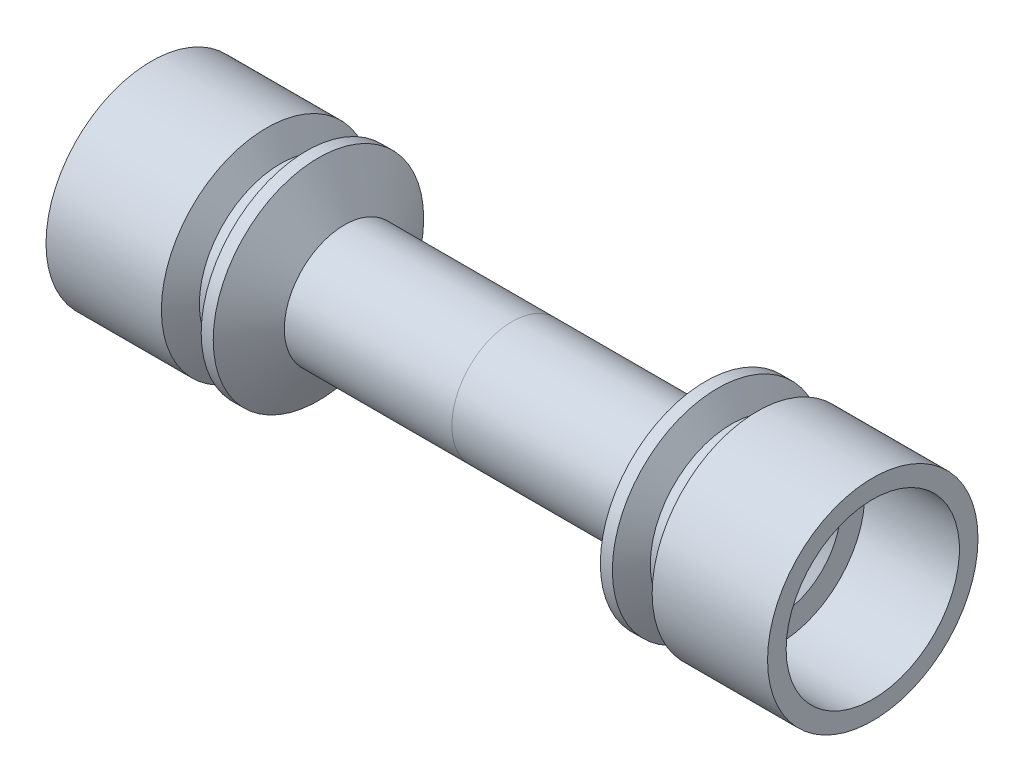
SolidWorks part; units mm, degrees
ref_plane "Front Plane" through (0, 0, 0) normal (0, 0, 1) x (1, 0, 0)
ref_plane "Top Plane" through (0, 0, 0) normal (0, 1, 0) x (1, 0, 0)
ref_plane "Right Plane" through (0, 0, 0) normal (1, 0, 0) x (0, 0, -1)
sketch "Sketch2" plane through (0, 0, 0) normal (0, 0, 1) x (1, 0, 0)
  line L0 (0, 0) -> (0, 28.4375) construction
  line L1 (-19.05, 4.575) -> (-14.05, 4.575) construction
  line L2 (-19.05, 4.575) -> (-19.05, -4.575) construction
  line L3 (-19.05, -4.575) -> (-14.05, -4.575) construction
  line L4 (-14.05, 4.575) -> (-14.05, -4.575) construction
  line L5 (-19.05, 4.575) -> (-14.05, -4.575) construction
  line L6 (-19.05, -4.575) -> (-14.05, 4.575) construction
  line L7 (14.05, 4.5) -> (49.5332, 4.5) construction
  line L8 (14.05, 4.5) -> (14.05, -4.5) construction
  line L9 (14.05, -4.5) -> (49.5332, -4.5) construction
  line L10 (49.5332, 4.5) -> (49.5332, -4.5) construction
  line L11 (14.05, 4.5) -> (49.5332, -4.5) construction
  line L12 (14.05, -4.5) -> (49.5332, 4.5) construction
  line L13 (-19.05, 0) -> (49.5332, 0) construction
  line L14 (-19.05, 5.5562) -> (-12.957, 5.5562)
  line L21 (-8.8457, 3.175) -> (0, 3.175)
  line L22 (-19.05, 5.5562) -> (-19.05, 4.575)
  line L23 (-19.05, 4.575) -> (-14.05, 4.575)
  line L24 (-14.05, 4.575) -> (-14.05, 0)
  line L25 (-14.05, 0) -> (0, 0)
  line L26 (0, 0) -> (0, 3.175)
  line L27 (-33.5594, -5.5562) -> (-33.5594, 5.5562) construction
  line L28 (-12.957, 5.5562) -> (-12.2238, 4.2863)
  line L29 (-12.2238, 4.2863) -> (-11.5887, 4.2863)
  line L30 (-19.05, 5.5562) -> (19.05, 5.5562) construction
  line L31 (0, 1.6) -> (-12.5, 1.6)
  line L32 (-12.5, 1.6) -> (-14.1, 0)
  line L33 (-12.5, 1.6) -> (-12.5, -1.6) construction
  line L34 (-12.5, 1.6) -> (12.5, 1.6) construction
  line L35 (-14.05, 1.7145) -> (-9.225, 1.7145)
  line L36 (-9.225, 1.7145) -> (-9.225, 0)
  line L37 (-14.05, 3.305) -> (-13.542, 2.797)
  line L38 (-9.225, 1.7145) -> (-22.225, 1.7145) construction
  line L39 (-9.225, 1.7145) -> (-9.225, -1.7145) construction
  line L40 (-9.225, -1.7145) -> (-22.225, -1.7145) construction
  line L41 (-22.225, 1.7145) -> (-22.225, -1.7145) construction
  line L42 (-13.542, 2.797) -> (-13.542, 0)
  line L46 (-11.5887, 4.2863) -> (-10.8555, 5.5563)
  line L47 (-10.8555, 5.5563) -> (-10.2205, 5.5563)
  line L48 (-10.2205, 5.5563) -> (-8.8457, 3.175)
  line L49 (-11.9062, 4.2863) -> (-11.9062, 6.3987) construction
  line L50 (-11.9062, 6.3987) -> (11.9062, 6.3987) construction
  point P0 (-16.55, 0)
  point P5 (31.7916, 0)
  point P27 (-33.5594, 0)
  point P28 (-18.8314, 6.3987)
  point P29 (-12.5, 0)
  point P33 (0, 6.3987)
  point P35 (-18.6093, 5.5562)
  point P36 (0, 1.6)
  point P48 (-9.225, 0)
  point P51 (0, 5.5562)
  point P52 (-20.4916, 6.5757)
  dimension "D3" = 3.175
  dimension "D4" = 11.1125
  dimension "D5" = 9.15
  dimension "D6" = 60
  dimension "D7" = 0.635
  dimension "D8" = 60
  dimension "D9" = 23.8125
  dimension "D10" = 1.27
  dimension "D11" = 38.1
  dimension "D12" = 0.635
  dimension "D13" = 45
  dimension "D14" = 25
  dimension "D15" = 3.2
  dimension "D16" = 3.429
  dimension "D17" = 3.175
  dimension "D18" = 1.27
  dimension "D19" = 0.508
  dimension "D20" = 45
  dimension "D21" = 13
  dimension "D22" = 5
revolve "Revolve1" add sketch "Sketch2" angle 360 about L13 region at (-9.3849, 3.2366, 0)
mirror "Mirror1" about plane through (0, 0, 0) normal (1, 0, 0) of bodies 101
chamfer "Chamfer1" distance 0.508 angle 45 1 edges at (-19.05, 0, 4.575)
